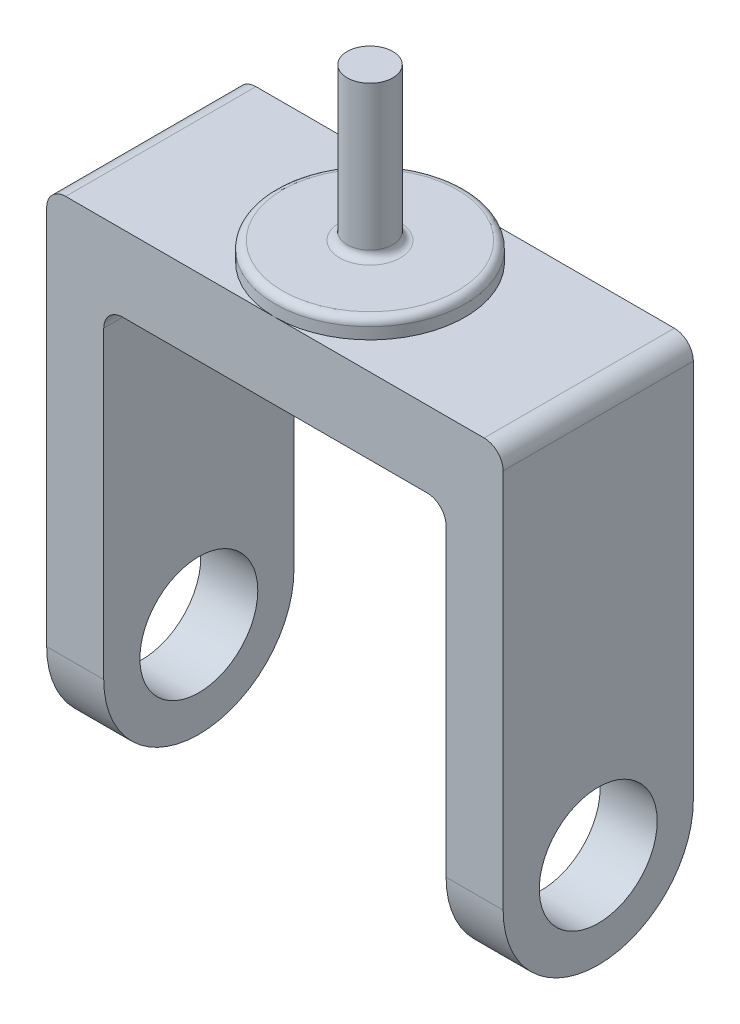
SolidWorks part; units mm, degrees
ref_plane "Front Plane" through (0, 0, 0) normal (0, 0, 1) x (1, 0, 0)
ref_plane "Top Plane" through (0, 0, 0) normal (0, 1, 0) x (1, 0, 0)
ref_plane "Right Plane" through (0, 0, 0) normal (1, 0, 0) x (0, 0, -1)
sketch "Sketch1" plane through (0, 0, 0) normal (0, 0, 1) x (1, 0, 0)
  line L1 (15, 118.7512) -> (105, 118.7512)
  line L2 (0, 0) -> (0, 138.7512)
  line L3 (0, 138.7512) -> (120, 138.7512)
  line L4 (120, 8.7512) -> (120, 138.7512)
  line L6 (0, 0) -> (0, 8.7512)
  line L7 (0, 8.7512) -> (15, 8.7512)
  line L8 (15, 118.7512) -> (15, 8.7512)
  line L11 (120, 8.7512) -> (105, 8.7512)
  line L12 (105, 118.7512) -> (105, 8.7512)
  dimension "D1" = 15
  dimension "D2" = 110
  dimension "." = 15
  dimension "D5" = 20
  dimension "60" = 90
extrude "Boss-Extrude1" add sketch "Sketch1" along normal blind 50 contours L1 L12 L11 L4 L3 L2 L7 L8 region at (13.2308, 63.7512, 0)
fillet "Fillet2" radius 25 1 edges at (7.5, 8.7512, 50) type face fillet first side face at (60, 68.7512, 50) second side face at (60, 68.7512, 0) second side face at (7.5, 8.7512, 25)
fillet "Fillet3" radius 25 1 edges at (7.5, 8.7512, 0) type face fillet first side face at (60, 68.7512, 0) second side face at (7.5, 8.7512, 12.5)
ref_plane "Plane1" through (60, 0, 0) normal (1, 0, 0) x (0, 0, -1)
fillet "Fillet4" radius 25 1 edges at (112.5, 8.7512, 50) type face fillet first side face at (60, 75.0012, 50) second side face at (112.5, 8.7512, 25)
fillet "Fillet5" radius 25 1 edges at (112.5, 8.7512, 0) type face fillet first side face at (60, 75.0012, 0) second side face at (112.5, 8.7512, 12.5)
sketch "Sketch2" plane through (120, 0, 0) normal (1, 0, 0) x (0, 0, -1)
  circle A1 centre (-25, 33.7512) radius 15.5
  arc A2 (-25, 8.7512) -> (0, 33.7512) centre (-25, 33.7512) ccw construction
  dimension "D1" = 31
extrude "Cut-Extrude1" cut sketch "Sketch2" against normal through all
sketch "Sketch3" plane through (0, 138.7512, 0) normal (0, 1, 0) x (1, 0, 0)
  line L0 (60, -27.5) -> (60, 27.5) construction
  circle A0 centre (60, -25) radius 25
  dimension "D1" = 50
extrude "Boss-Extrude2" add sketch "Sketch3" along normal blind 5
sketch "Sketch4" plane through (0, 143.7512, 0) normal (0, 1, 0) x (1, 0, 0)
  circle A0 centre (60, -25) radius 6
  circle A1 centre (60, -25) radius 25 construction
  dimension "D1" = 12
extrude "Boss-Extrude3" add sketch "Sketch4" along normal blind 40
fillet "Fillet6" radius 2 2 edges at (60, 143.7512, 50) (60, 143.7512, 31)
fillet "Fillet7" radius 5 4 edges at (0, 138.7512, 25) (120, 138.7512, 25) (15, 118.7512, 25) (105, 118.7512, 25)
